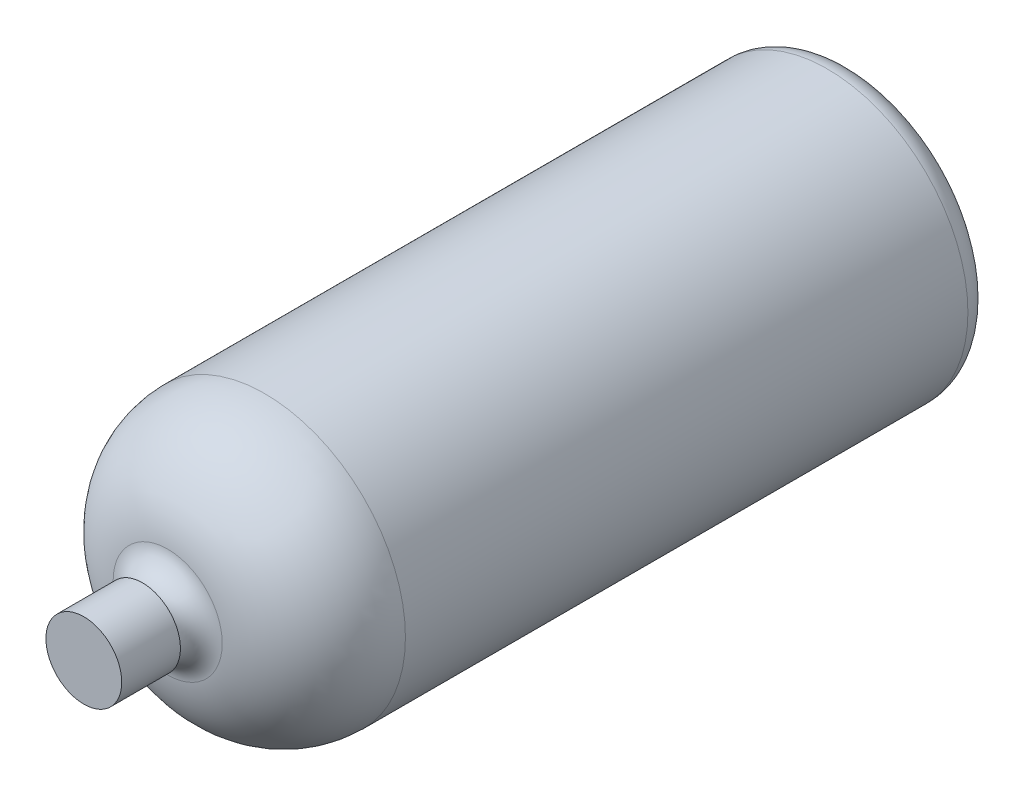
SolidWorks part; units mm, degrees
ref_plane "Front Plane" through (0, 0, 0) normal (0, 0, 1) x (1, 0, 0)
ref_plane "Top Plane" through (0, 0, 0) normal (0, 1, 0) x (1, 0, 0)
ref_plane "Right Plane" through (0, 0, 0) normal (1, 0, 0) x (0, 0, -1)
sketch "Sketch1" plane through (0, 0, 0) normal (0, 0, 1) x (1, 0, 0)
  circle A0 centre (0, 0) radius 57.5
  dimension "D1" = 115
extrude "Boss-Extrude1" add sketch "Sketch1" along normal blind 280
fillet "Fillet1" radius 40 1 edges at (57.5, 0, 280)
sketch "Sketch2" plane through (0, 0, 280) normal (0, 0, 1) x (1, 0, 0)
  circle A0 centre (0, 0) radius 13.5
  dimension "D1" = 27
extrude "Boss-Extrude2" add sketch "Sketch2" along normal blind 10
sketch "Sketch3" plane through (0, 0, 290) normal (0, 0, 1) x (1, 0, 0)
  circle A0 centre (0, 0) radius 15.5
  dimension "D1" = 31
extrude "Boss-Extrude3" add sketch "Sketch3" along normal blind 24
fillet "Fillet2" radius 10 1 edges at (13.5, 0, 280)
fillet "Fillet3" radius 10 1 edges at (57.5, 0, 0)
